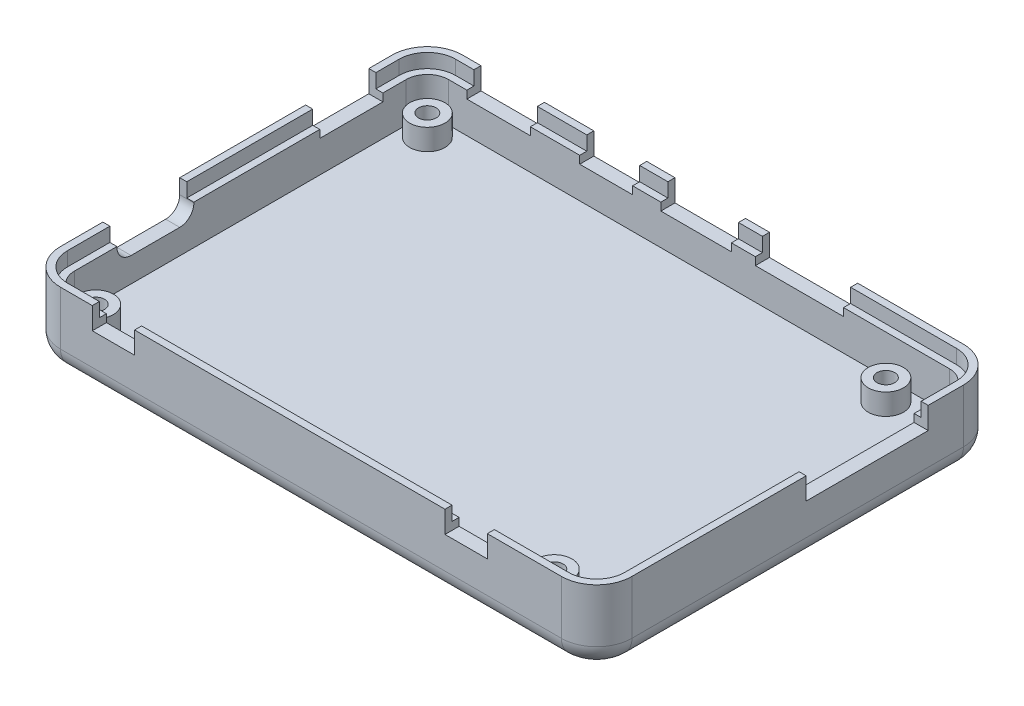
SolidWorks part; units mm, degrees
ref_plane "前视基准面" through (0, 0, 0) normal (0, 0, 1) x (1, 0, 0)
ref_plane "上视基准面" through (0, 0, 0) normal (0, 1, 0) x (1, 0, 0)
ref_plane "右视基准面" through (0, 0, 0) normal (1, 0, 0) x (0, 0, -1)
sketch "草图4" plane through (0, 0, 0) normal (0, 1, 0) x (1, 0, 0)
  line L1 (-118.546, 139.5567) -> (-41.546, 139.5567)
  line L2 (-118.546, 139.5567) -> (-118.546, 86.5567)
  line L3 (-118.546, 86.5567) -> (-41.546, 86.5567)
  line L4 (-41.546, 139.5567) -> (-41.546, 86.5567)
  line L5 (-39.546, 141.5567) -> (-39.546, 84.5567)
  line L6 (-120.546, 84.5567) -> (-39.546, 84.5567)
  line L7 (-120.546, 141.5567) -> (-120.546, 84.5567)
  line L8 (-120.546, 141.5567) -> (-39.546, 141.5567)
  circle A0 centre (-115.546, 136.5567) radius 1.25
  circle A1 centre (-50.546, 136.5567) radius 1.25
  circle A2 centre (-50.546, 89.5567) radius 1.25
  circle A3 centre (-115.546, 89.5567) radius 1.25
  circle A4 centre (-115.546, 136.5567) radius 2.5
  circle A5 centre (-50.546, 136.5567) radius 2.5
  circle A6 centre (-50.546, 89.5567) radius 2.5
  circle A7 centre (-115.546, 89.5567) radius 2.5
  dimension "D3" = 5
  dimension "D4" = 5
  dimension "D5" = 5
  dimension "D6" = 5
  dimension "D7" = 2.5
  dimension "D9" = 3
  dimension "D1" = 77
  dimension "D2" = 53
  dimension "D8" = 3
  dimension "D10" = 2
extrude "凸台-拉伸5" add sketch "草图4" along normal blind 3 contours A0 | A1 | A2 | A3 | L5 L6 L7 L8 region at (-115.546, 0, -136.5567) region at (-50.546, 0, -136.5567) region at (-50.546, 0, -89.5567) region at (-115.546, 0, -89.5567)
extrude "凸台-拉伸6" add sketch "草图4<4>" along normal blind 3 from surface contours A6 A2 | A7 A3 | A5 A1 | A4 A0 region at (-117.9753, 0, -136.5567) region at (-52.9753, 0, -136.5567) region at (-52.9753, 0, -89.5567) region at (-117.9753, 0, -89.5567) starting at face at (-80.046, 3, -113.0567)
sketch "草图4<4>" plane through (0, 0, 0) normal (0, 1, 0) x (1, 0, 0) same geometry as "草图4"
extrude "凸台-拉伸7" add sketch "草图4<5>" along normal blind 10.6 contours L8 L7 L6 L5 L1 L4 L3 L2 region at (-40.5364, 0, -113.0567)
sketch "草图4<5>" plane through (0, 0, 0) normal (0, 1, 0) x (1, 0, 0) same geometry as "草图4"
sketch "草图6" plane through (0, 0, -141.5567) normal (0, 0, -1) x (-1, 0, 0)
  line L0 (120.546, 10.6) -> (39.546, 10.6) construction
  line L1 (59.546, 10.6) -> (72.046, 10.6)
  line L2 (59.546, 10.6) -> (59.546, 7.5)
  line L3 (59.546, 7.5) -> (72.046, 7.5)
  line L4 (72.046, 10.6) -> (72.046, 7.5)
  line L6 (75.446, 10.6) -> (85.446, 10.6)
  line L7 (75.446, 10.6) -> (75.446, 7.5)
  line L8 (75.446, 7.5) -> (85.446, 7.5)
  line L9 (85.446, 10.6) -> (85.446, 7.5)
  line L10 (89.446, 10.6) -> (96.946, 10.6)
  line L11 (89.446, 10.6) -> (89.446, 7.5)
  line L12 (89.446, 7.5) -> (96.946, 7.5)
  line L13 (96.946, 10.6) -> (96.946, 7.5)
  line L14 (103.946, 10.6) -> (112.946, 10.6)
  line L15 (103.946, 10.6) -> (103.946, 7.5)
  line L16 (103.946, 7.5) -> (112.946, 7.5)
  line L17 (112.946, 10.6) -> (112.946, 7.5)
  line L23 (39.546, 10.6) -> (39.546, 0) construction
  dimension "D1" = 12.5
  dimension "D2" = 20
  dimension "D3" = 3.4
  dimension "D4" = 10
  dimension "D5" = 4
  dimension "D6" = 7.5
  dimension "D7" = 3.1
  dimension "D8" = 9
  dimension "D9" = 7
extrude "切除-拉伸1" cut sketch "草图6" against normal blind 2
sketch "草图7" plane through (-120.546, 0, 0) normal (-1, 0, 0) x (0, 0, 1)
  line L0 (-141.5567, 10.6) -> (-84.5567, 10.6) construction
  line L1 (-133.2567, 10.6) -> (-124.3067, 10.6)
  line L2 (-133.2567, 10.6) -> (-133.2567, 7.5)
  line L3 (-133.2567, 7.5) -> (-124.3067, 7.5)
  line L4 (-124.3067, 10.6) -> (-124.3067, 7.5)
  line L5 (-84.5567, 10.6) -> (-84.5567, 0) construction
  line L6 (-105.4567, 10.6) -> (-96.5567, 10.6)
  line L7 (-105.4567, 10.6) -> (-105.4567, 7.5)
  line L8 (-105.4567, 7.5) -> (-96.5567, 7.5)
  line L9 (-96.5567, 10.6) -> (-96.5567, 7.5)
  line L10 (-141.5567, 10.6) -> (-141.5567, 0) construction
  line L11 (-106.4567, 11.6) -> (-95.5567, 11.6)
  line L12 (-95.5567, 11.6) -> (-95.5567, 6.5)
  line L13 (-106.4567, 6.5) -> (-95.5567, 6.5)
  line L14 (-106.4567, 11.6) -> (-106.4567, 6.5)
  point P12 (-133.2567, 9.05)
  line M5 (-84.5567, 10.6) -> (-141.5567, 10.6)
  dimension "D1" = 12
  dimension "D2" = 8.95
  dimension "D3" = 8.3
  dimension "D4" = 8.9
  dimension "D5" = 3.1
  dimension "D6" = 1
extrude "切除-拉伸2" cut sketch "草图7" against normal blind 2 contours L4 L2 L3 M5 | L9 L7 L8 M5 | L14 L13 L12 L9 L8 L7 M5 region at (-120.546, 10.4835, -105.9567) region at (-120.546, 9.05, -128.7817) region at (-120.546, 9.05, -101.0067)
fillet "圆角1" radius 2 2 edges at (-119.546, 6.5, -95.5567) (-119.546, 6.5, -106.4567)
sketch "草图8" plane through (0, 0, -84.5567) normal (0, 0, 1) x (1, 0, 0)
  line L0 (-120.546, 10.6) -> (-39.546, 10.6) construction
  line L1 (-111.046, 10.6) -> (-105.046, 10.6)
  line L2 (-111.046, 10.6) -> (-111.046, 7.5)
  line L3 (-111.046, 7.5) -> (-105.046, 7.5)
  line L4 (-105.046, 10.6) -> (-105.046, 7.5)
  line L5 (-39.546, 10.6) -> (-39.546, 0) construction
  line L6 (-61.046, 10.6) -> (-55.046, 10.6)
  line L7 (-61.046, 10.6) -> (-61.046, 7.5)
  line L8 (-61.046, 7.5) -> (-55.046, 7.5)
  line L9 (-55.046, 10.6) -> (-55.046, 7.5)
  line L10 (-120.546, 10.6) -> (-120.546, 0) construction
  dimension "D1" = 6
  dimension "D2" = 6
  dimension "D3" = 15.5
  dimension "D4" = 9.5
  dimension "D5" = 3.1
extrude "切除-拉伸3" cut sketch "草图8" against normal blind 2
sketch "草图9" plane through (-39.546, 0, 0) normal (1, 0, 0) x (0, 0, -1)
  line L0 (141.5567, 10.6) -> (84.5567, 10.6) construction
  line L1 (114.2567, 10.6) -> (131.5567, 10.6)
  line L2 (114.2567, 10.6) -> (114.2567, 7.5)
  line L3 (114.2567, 7.5) -> (131.5567, 7.5)
  line L4 (131.5567, 10.6) -> (131.5567, 7.5)
  line L5 (141.5567, 10.6) -> (141.5567, 0) construction
  dimension "D1" = 10
  dimension "D2" = 17.3
  dimension "D3" = 3.1
extrude "切除-拉伸4" cut sketch "草图9" against normal blind 2
fillet "圆角2" radius 3 4 edges at (-41.546, 6.8, -86.5567) (-41.546, 6.8, -139.5567) (-118.546, 6.8, -139.5567) (-118.546, 6.8, -86.5567)
fillet "圆角3" radius 5 4 edges at (-120.546, 5.3, -84.5567) (-39.546, 5.3, -84.5567) (-39.546, 5.3, -141.5567) (-120.546, 5.3, -141.5567)
fillet "圆角4" radius 3 8 edges at (-119.0815, 0, -86.0211) (-120.546, 0, -113.0567) (-119.0815, 0, -140.0922) (-80.046, 0, -141.5567) (-41.0104, 0, -140.0922) (-39.546, 0, -113.0567) (-41.0104, 0, -86.0211) (-80.046, 0, -84.5567)
sketch "草图10" plane through (0, 0, 0) normal (0, -1, 0) x (1, 0, 0)
  line L1 (-48.046, -89.5567) -> (-49.296, -87.3916)
  line L2 (-49.296, -87.3916) -> (-51.796, -87.3916)
  line L3 (-51.796, -87.3916) -> (-53.046, -89.5567)
  line L4 (-53.046, -89.5567) -> (-51.796, -91.7217)
  line L5 (-51.796, -91.7217) -> (-49.296, -91.7217)
  line L6 (-49.296, -91.7217) -> (-48.046, -89.5567)
  line L7 (-113.046, -89.5567) -> (-114.296, -87.3916)
  line L8 (-114.296, -87.3916) -> (-116.796, -87.3916)
  line L9 (-116.796, -87.3916) -> (-118.046, -89.5567)
  line L10 (-118.046, -89.5567) -> (-116.796, -91.7217)
  line L11 (-116.796, -91.7217) -> (-114.296, -91.7217)
  line L12 (-114.296, -91.7217) -> (-113.046, -89.5567)
  line L13 (-113.046, -136.5567) -> (-114.296, -134.3916)
  line L14 (-114.296, -134.3916) -> (-116.796, -134.3916)
  line L15 (-116.796, -134.3916) -> (-118.046, -136.5567)
  line L16 (-118.046, -136.5567) -> (-116.796, -138.7217)
  line L17 (-116.796, -138.7217) -> (-114.296, -138.7217)
  line L18 (-114.296, -138.7217) -> (-113.046, -136.5567)
  line L19 (-48.046, -136.5567) -> (-49.296, -134.3916)
  line L20 (-49.296, -134.3916) -> (-51.796, -134.3916)
  line L21 (-51.796, -134.3916) -> (-53.046, -136.5567)
  line L22 (-53.046, -136.5567) -> (-51.796, -138.7217)
  line L23 (-51.796, -138.7217) -> (-49.296, -138.7217)
  line L24 (-49.296, -138.7217) -> (-48.046, -136.5567)
  circle A0 centre (-50.546, -89.5567) radius 2.1651 construction
  circle A1 centre (-115.546, -89.5567) radius 2.1651 construction
  circle A2 centre (-115.546, -136.5567) radius 2.1651 construction
  circle A3 centre (-50.546, -136.5567) radius 2.1651 construction
  dimension "D1" = 5
  dimension "D2" = 5
  dimension "D3" = 5
  dimension "D4" = 5
extrude "切除-拉伸5" cut sketch "草图10" against normal blind 2
sketch "草图11" plane through (0, 10.6, 0) normal (0, 1, 0) x (1, 0, 0)
  line L1 (-115.546, 140.5567) -> (-44.546, 140.5567)
  line L2 (-119.546, 136.5567) -> (-119.546, 89.5567)
  line L3 (-115.546, 85.5567) -> (-44.546, 85.5567)
  line L4 (-40.546, 136.5567) -> (-40.546, 89.5567)
  line L5 (-119.546, 140.5567) -> (-40.546, 85.5567) construction
  line L6 (-119.546, 85.5567) -> (-40.546, 140.5567) construction
  line L8 (-115.546, 86.5567) -> (-44.546, 86.5567) construction
  line L9 (-118.546, 136.5567) -> (-118.546, 89.5567) construction
  line L10 (-120.546, 124.3067) -> (-120.546, 106.4567) construction
  line L11 (-103.946, 141.5567) -> (-96.946, 141.5567) construction
  line L12 (-115.546, 139.5567) -> (-44.546, 139.5567)
  line L13 (-41.546, 136.5567) -> (-41.546, 89.5567)
  line L14 (-115.546, 86.5567) -> (-44.546, 86.5567)
  line L15 (-118.546, 136.5567) -> (-118.546, 89.5567)
  line L16 (-118.9746, 141.3774) -> (-39.9746, 86.3774)
  line L17 (-120.1173, 86.3774) -> (-41.1173, 141.3774)
  arc A0 (-115.546, 140.5567) -> (-119.546, 136.5567) centre (-115.546, 136.5567) ccw
  arc A1 (-119.546, 89.5567) -> (-115.546, 85.5567) centre (-115.546, 89.5567) ccw
  arc A2 (-44.546, 85.5567) -> (-40.546, 89.5567) centre (-44.546, 89.5567) ccw
  arc A3 (-44.546, 140.5567) -> (-40.546, 136.5567) centre (-44.546, 136.5567) cw
  arc A4 (-44.546, 139.5567) -> (-41.546, 136.5567) centre (-44.546, 136.5567) cw
  arc A5 (-44.546, 86.5567) -> (-41.546, 89.5567) centre (-44.546, 89.5567) ccw
  arc A6 (-118.546, 89.5567) -> (-115.546, 86.5567) centre (-115.546, 89.5567) ccw
  arc A7 (-115.546, 139.5567) -> (-118.546, 136.5567) centre (-115.546, 136.5567) ccw
  point P0 (-80.046, 113.0567)
  point P5 (0, 0)
  point P6 (0, 0)
  point P8 (0, 0)
  point P10 (-80.046, 86.5567)
  point P11 (-81.4269, 112.811)
  point P14 (-118.546, 113.0567)
  line M3 (-61.046, 84.5567) -> (-61.046, 86.5567)
  line M4 (-61.046, 86.5567) -> (-105.046, 86.5567)
  line M5 (-105.046, 86.5567) -> (-105.046, 84.5567)
  dimension "D3" = 4
  dimension "D4" = 4
  dimension "D1" = 1
  dimension "D2" = 1
  dimension "D5" = 1
extrude "切除-拉伸6" cut sketch "草图11" against normal blind 2 contours A5 L14 L3 A2 L16 M3 | A5 L16 A2 L4 A3 L17 A4 L13 | A7 L12 A4 L17 A3 L1 A0 L16 | A7 L16 A0 L2 A1 L17 A6 L15 | A6 L17 A1 L3 L14 M5 | L3 M5 M3 M4 region at (-80.046, 10.6, -140.0563) region at (-118.9752, 10.6, -114.1041) region at (-41.1167, 10.6, -114.1041) region at (-51.1297, 10.6, -86.1409) region at (-111.9538, 10.6, -86.1774) region at (-83.046, 10.6, -86.0567)
